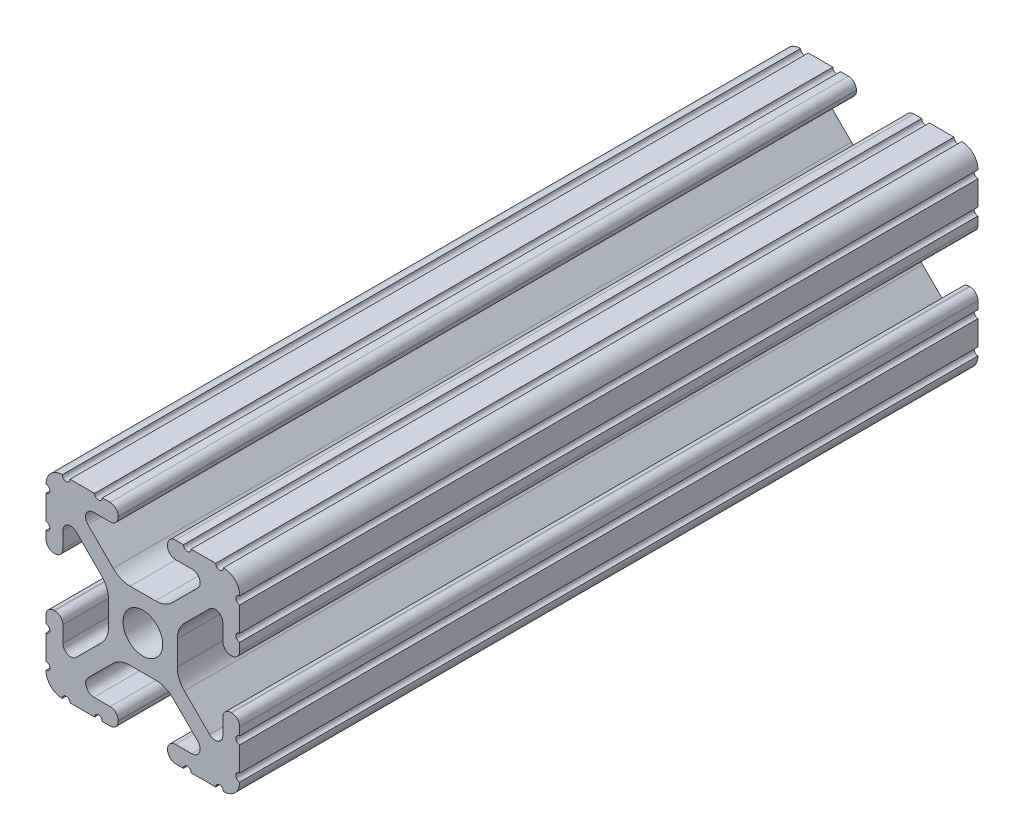
SolidWorks part; units mm, degrees
ref_plane "Front" through (0, 0, 0) normal (0, 0, 1) x (1, 0, 0)
ref_plane "Top" through (0, 0, 0) normal (0, 1, 0) x (1, 0, 0)
ref_plane "Right" through (0, 0, 0) normal (1, 0, 0) x (0, 0, -1)
sketch "Sketch1" plane through (0, 0, 0) normal (0, 0, 1) x (1, 0, 0)
  line L0 (-7.5107, 9.4563) -> (7.5107, 9.4563) construction
  line L1 (-7.4968, -9.4098) -> (7.4968, -9.4098) construction
  line L88 (-7.1797, -8.6452) -> (-3.9523, -5.4237)
  line L89 (-1.7093, -4.4958) -> (1.7093, -4.4958)
  line L90 (3.9523, -5.4237) -> (7.1797, -8.6452)
  line L91 (6.4164, -10.4902) -> (4.2875, -10.4902)
  line L92 (3.2385, -11.5392) -> (3.2385, -11.651)
  line L93 (4.2875, -12.7) -> (5.3171, -12.7)
  line L94 (6.3331, -12.7) -> (9.5504, -12.7)
  line L95 (12.7, -9.5504) -> (12.7, -6.3331)
  line L96 (12.7, -5.3171) -> (12.7, -4.2875)
  line L97 (11.651, -3.2385) -> (11.5392, -3.2385)
  line L98 (10.4902, -4.2875) -> (10.4902, -6.4021)
  line L99 (8.7371, -7.1294) -> (5.441, -3.8408)
  line L100 (4.5085, -1.5932) -> (4.5085, 1.5932)
  line L101 (5.441, 3.8408) -> (8.7371, 7.1294)
  line L102 (10.4902, 6.4021) -> (10.4902, 4.2875)
  line L103 (11.5392, 3.2385) -> (11.651, 3.2385)
  line L104 (12.7, 4.2875) -> (12.7, 5.3171)
  line L105 (12.7, 6.3331) -> (12.7, 9.5504)
  line L106 (9.5504, 12.7) -> (6.3331, 12.7)
  line L107 (5.3171, 12.7) -> (4.2875, 12.7)
  line L108 (3.2385, 11.651) -> (3.2385, 11.5392)
  line L109 (4.2875, 10.4902) -> (6.4768, 10.4902)
  line L110 (7.207, 8.7244) -> (3.8983, 5.4232)
  line L111 (1.6558, 4.4958) -> (-1.6558, 4.4958)
  line L112 (-3.8983, 5.4232) -> (-7.207, 8.7244)
  line L113 (-6.4768, 10.4902) -> (-4.2875, 10.4902)
  line L114 (-3.2385, 11.5392) -> (-3.2385, 11.651)
  line L115 (-4.2875, 12.7) -> (-5.3171, 12.7)
  line L116 (-6.3331, 12.7) -> (-9.5504, 12.7)
  line L117 (-12.7, 9.5504) -> (-12.7, 6.3331)
  line L118 (-12.7, 5.3171) -> (-12.7, 4.2875)
  line L119 (-11.651, 3.2385) -> (-11.5392, 3.2385)
  line L120 (-10.4902, 4.2875) -> (-10.4902, 6.4021)
  line L121 (-8.7371, 7.1294) -> (-5.441, 3.8408)
  line L122 (-4.5085, 1.5932) -> (-4.5085, -1.5932)
  line L123 (-5.441, -3.8408) -> (-8.7371, -7.1294)
  line L124 (-10.4902, -6.4021) -> (-10.4902, -4.2875)
  line L125 (-11.5392, -3.2385) -> (-11.651, -3.2385)
  line L126 (-12.7, -4.2875) -> (-12.7, -5.3171)
  line L127 (-12.7, -6.3331) -> (-12.7, -9.5504)
  line L128 (-9.5504, -12.7) -> (-6.3331, -12.7)
  line L129 (-5.3171, -12.7) -> (-4.2875, -12.7)
  line L130 (-3.2385, -11.651) -> (-3.2385, -11.5392)
  line L131 (-4.2875, -10.4902) -> (-6.4164, -10.4902)
  circle A1 centre (0, 0) radius 2.6035
  arc A104 (-7.1797, -8.6452) -> (-6.4164, -10.4902) centre (-6.4164, -9.4098) ccw
  arc A105 (-1.7093, -4.4958) -> (-3.9523, -5.4237) centre (-1.7093, -7.6708) ccw
  arc A106 (3.9523, -5.4237) -> (1.7093, -4.4958) centre (1.7093, -7.6708) ccw
  arc A107 (6.4164, -10.4902) -> (7.1797, -8.6452) centre (6.4164, -9.4098) ccw
  arc A108 (4.2875, -10.4902) -> (3.2385, -11.5392) centre (4.2875, -11.5392) ccw
  arc A109 (3.2385, -11.651) -> (4.2875, -12.7) centre (4.2875, -11.651) ccw
  arc A110 (6.3331, -12.7) -> (5.3171, -12.7) centre (5.8251, -12.7) ccw
  arc A111 (10.5664, -12.6998) -> (9.5504, -12.7) centre (10.0584, -12.7) ccw
  arc A112 (10.5664, -12.6998) -> (12.6998, -10.5664) centre (10.5918, -10.5918) ccw
  arc A113 (12.7, -9.5504) -> (12.6998, -10.5664) centre (12.7, -10.0584) ccw
  arc A114 (12.7, -5.3171) -> (12.7, -6.3331) centre (12.7, -5.8251) ccw
  arc A115 (12.7, -4.2875) -> (11.651, -3.2385) centre (11.651, -4.2875) ccw
  arc A116 (11.5392, -3.2385) -> (10.4902, -4.2875) centre (11.5392, -4.2875) ccw
  arc A117 (8.7371, -7.1294) -> (10.4902, -6.4021) centre (9.4628, -6.4021) ccw
  arc A118 (4.5085, -1.5932) -> (5.441, -3.8408) centre (7.6835, -1.5932) ccw
  arc A119 (5.441, 3.8408) -> (4.5085, 1.5932) centre (7.6835, 1.5932) ccw
  arc A120 (10.4902, 6.4021) -> (8.7371, 7.1294) centre (9.4628, 6.4021) ccw
  arc A121 (10.4902, 4.2875) -> (11.5392, 3.2385) centre (11.5392, 4.2875) ccw
  arc A122 (11.651, 3.2385) -> (12.7, 4.2875) centre (11.651, 4.2875) ccw
  arc A123 (12.7, 6.3331) -> (12.7, 5.3171) centre (12.7, 5.8251) ccw
  arc A124 (12.6998, 10.5664) -> (12.7, 9.5504) centre (12.7, 10.0584) ccw
  arc A125 (12.6998, 10.5664) -> (10.5664, 12.6998) centre (10.5918, 10.5918) ccw
  arc A126 (9.5504, 12.7) -> (10.5664, 12.6998) centre (10.0584, 12.7) ccw
  arc A127 (5.3171, 12.7) -> (6.3331, 12.7) centre (5.8251, 12.7) ccw
  arc A128 (4.2875, 12.7) -> (3.2385, 11.651) centre (4.2875, 11.651) ccw
  arc A129 (3.2385, 11.5392) -> (4.2875, 10.4902) centre (4.2875, 11.5392) ccw
  arc A130 (7.207, 8.7244) -> (6.4768, 10.4902) centre (6.4768, 9.4563) ccw
  arc A131 (1.6558, 4.4958) -> (3.8983, 5.4232) centre (1.6558, 7.6708) ccw
  arc A132 (-3.8983, 5.4232) -> (-1.6558, 4.4958) centre (-1.6558, 7.6708) ccw
  arc A133 (-6.4768, 10.4902) -> (-7.207, 8.7244) centre (-6.4768, 9.4563) ccw
  arc A134 (-4.2875, 10.4902) -> (-3.2385, 11.5392) centre (-4.2875, 11.5392) ccw
  arc A135 (-3.2385, 11.651) -> (-4.2875, 12.7) centre (-4.2875, 11.651) ccw
  arc A136 (-6.3331, 12.7) -> (-5.3171, 12.7) centre (-5.8251, 12.7) ccw
  arc A137 (-10.5664, 12.6998) -> (-9.5504, 12.7) centre (-10.0584, 12.7) ccw
  arc A138 (-10.5664, 12.6998) -> (-12.6998, 10.5664) centre (-10.5918, 10.5918) ccw
  arc A139 (-12.7, 9.5504) -> (-12.6998, 10.5664) centre (-12.7, 10.0584) ccw
  arc A140 (-12.7, 5.3171) -> (-12.7, 6.3331) centre (-12.7, 5.8251) ccw
  arc A141 (-12.7, 4.2875) -> (-11.651, 3.2385) centre (-11.651, 4.2875) ccw
  arc A142 (-11.5392, 3.2385) -> (-10.4902, 4.2875) centre (-11.5392, 4.2875) ccw
  arc A143 (-8.7371, 7.1294) -> (-10.4902, 6.4021) centre (-9.4628, 6.4021) ccw
  arc A144 (-4.5085, 1.5932) -> (-5.441, 3.8408) centre (-7.6835, 1.5932) ccw
  arc A145 (-5.441, -3.8408) -> (-4.5085, -1.5932) centre (-7.6835, -1.5932) ccw
  arc A146 (-10.4902, -6.4021) -> (-8.7371, -7.1294) centre (-9.4628, -6.4021) ccw
  arc A147 (-10.4902, -4.2875) -> (-11.5392, -3.2385) centre (-11.5392, -4.2875) ccw
  arc A148 (-11.651, -3.2385) -> (-12.7, -4.2875) centre (-11.651, -4.2875) ccw
  arc A149 (-12.7, -6.3331) -> (-12.7, -5.3171) centre (-12.7, -5.8251) ccw
  arc A150 (-12.6998, -10.5664) -> (-12.7, -9.5504) centre (-12.7, -10.0584) ccw
  arc A151 (-12.6998, -10.5664) -> (-10.5664, -12.6998) centre (-10.5918, -10.5918) ccw
  arc A152 (-9.5504, -12.7) -> (-10.5664, -12.6998) centre (-10.0584, -12.7) ccw
  arc A153 (-5.3171, -12.7) -> (-6.3331, -12.7) centre (-5.8251, -12.7) ccw
  arc A154 (-4.2875, -12.7) -> (-3.2385, -11.651) centre (-4.2875, -11.651) ccw
  arc A155 (-3.2385, -11.5392) -> (-4.2875, -10.4902) centre (-4.2875, -11.5392) ccw
extrude "Boss-Extrude1" add sketch "Sketch1" along normal mid plane 914.4
sketch "Sketch3" plane through (-12.7, 0, 0) normal (-1, 0, 0) x (0, 0, 1)
  line L0 (-203.2, -25.4) -> (-203.2, 21.1581) construction
  line L1 (-203.2, -27.5528) -> (-203.2, 21.1581)
  line L2 (-203.2, 21.1581) -> (-461.0909, 21.1581)
  line L3 (-461.0909, 21.1581) -> (-461.0909, -25.4)
  line L4 (-461.0909, -25.4) -> (-203.2, -27.5528)
extrude "Cut-Extrude2" cut sketch "Sketch3" against normal blind 26.924 and the other way blind 4.318
sketch "Sketch4" plane through (12.7, 0, 0) normal (1, 0, 0) x (0, 0, -1)
  line L0 (106.4068, 27.2984) -> (106.4068, -39.7635) construction
  line L1 (106.4068, 13.9899) -> (106.4068, -36.6295)
  line L2 (106.4068, -36.6295) -> (-460.1585, -34.1333)
  line L3 (-460.1585, -34.1333) -> (-460.1585, 13.9899)
  line L4 (106.4068, 13.9899) -> (-460.1585, 13.9899)
  point P5 (99.8262, 27.2984)
extrude "Cut-Extrude3" cut sketch "Sketch4" against normal through all
